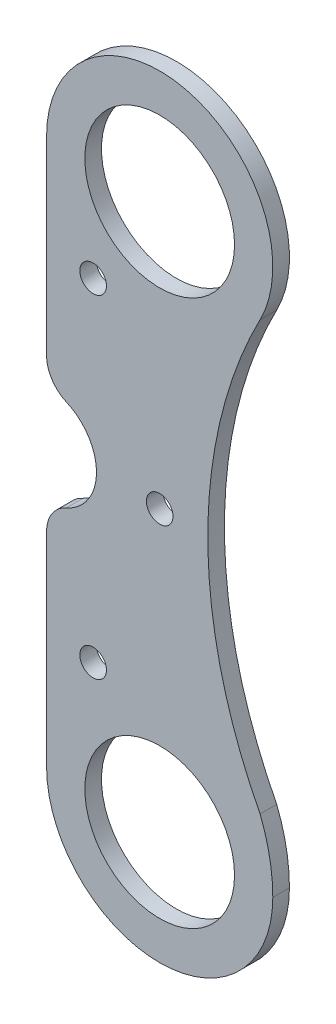
SolidWorks part; units mm, degrees
material "6061 Alloy"
ref_plane "Front Plane" through (0, 0, 0) normal (0, 0, 1) x (1, 0, 0)
ref_plane "Top Plane" through (0, 0, 0) normal (0, 1, 0) x (1, 0, 0)
ref_plane "Right Plane" through (0, 0, 0) normal (1, 0, 0) x (0, 0, -1)
sketch "Sketch1" plane through (0, 0, 0) normal (0, 0, 1) x (1, 0, 0)
  line L0 (0, 0) -> (0, -101.6) construction
  line L1 (21.59, -120.5575) -> (-21.59, -120.5575) construction
  line L2 (-8.89, 25.4) -> (8.89, 25.4)
  line L3 (-21.59, 12.7) -> (-21.59, -117.7751)
  line L5 (21.59, 12.7) -> (21.59, -117.7751)
  line L9 (-23.3829, -122.6853) -> (-33.2033, -134.3394)
  line L10 (-36.322, 25.4) -> (20.828, 25.4) construction
  line L11 (-36.322, 25.4) -> (-36.322, -203.2) construction
  line L12 (-36.322, -203.2) -> (20.828, -203.2) construction
  line L13 (20.828, 25.4) -> (20.828, -203.2) construction
  line L15 (-7.9527, -155.6168) -> (19.7971, -122.6853)
  line L16 (-32.4392, -143.2871) -> (-16.9004, -156.3809)
  circle A0 centre (0, 0) radius 38.1 construction
  circle A1 centre (0, -101.6) radius 38.1 construction
  circle A2 centre (0, 0) radius 14.2875
  circle A3 centre (0, -101.6) radius 14.2875
  arc A6 (8.89, 25.4) -> (21.59, 12.7) centre (8.89, 12.7) cw
  arc A7 (-8.89, 25.4) -> (-21.59, 12.7) centre (-8.89, 12.7) ccw
  circle A10 centre (-18.5321, -142.5501) radius 2.54
  arc A13 (-23.3829, -122.6853) -> (-21.59, -117.7751) centre (-29.21, -117.7751) ccw
  arc A14 (19.7971, -122.6853) -> (21.59, -117.7751) centre (13.97, -117.7751) ccw
  arc A15 (-16.9004, -156.3809) -> (-7.9527, -155.6168) centre (-12.8086, -151.525) ccw
  arc A16 (-33.2033, -134.3394) -> (-32.4392, -143.2871) centre (-28.3474, -138.4312) ccw
  circle A17 centre (0, -50.8) radius 2.54
  point P13 (-192.705, 39.2708)
  point P20 (21.59, 25.4)
  point P23 (-21.59, 25.4)
  point P31 (-36.322, -138.0404)
  dimension "D2" = 76.2
  dimension "D3" = 76.2
  dimension "D4" = 28.575
  dimension "D5" = 28.575
  dimension "D10" = 228.6
  dimension "D11" = 36.322
  dimension "D13" = 5.08
  dimension "D19" = 6.35
  dimension "D20" = 7.62
  dimension "D21" = 12.7
  dimension "D22" = 5.08
  dimension "D1" = 101.6
  dimension "D6" = 43.18
  dimension "D7" = 21.59
  dimension "D8" = 25.4
  dimension "D9" = 57.15
  dimension "D12" = 25.4
  dimension "D14" = 33.02
  dimension "D15" = 16.51
  dimension "D16" = 21.59
  dimension "D17" = 9.525
  dimension "D18" = 18.9575
extrude "Boss-Extrude1" add sketch "Sketch1" along normal blind 3.175
sketch "Sketch2" plane through (0, 0, 0) normal (0, 0, 1) x (1, 0, 0)
  line L0 (-21.59, -41.275) -> (-21.59, -60.325)
  line L1 (0, 0) -> (0, -101.6) construction
  line L4 (21.59, -117.7751) -> (21.59, 12.7) construction
  line L5 (-21.59, -50.8) -> (97.79, -50.8) construction
  line L6 (-21.59, 12.7) -> (-21.59, -117.7751) construction
  line L7 (0, 0) -> (-39.9512, 0) construction
  line L9 (16.51, -115.5122) -> (-17.5013, -155.8745)
  line L10 (-32.4392, -143.2871) -> (-16.9004, -156.3809) construction
  line L11 (-7.9527, -155.6168) -> (19.7971, -122.6853) construction
  line L13 (27.94, -121.6567) -> (-7.6203, -163.8572)
  line L14 (-7.6203, -163.8572) -> (-17.5013, -155.8745)
  line L15 (27.94, -121.6567) -> (27.94, 0)
  line L16 (27.94, 0) -> (21.59, 0)
  arc A1 (19.1591, -91.6472) -> (19.1591, -9.9528) centre (97.79, -50.8) cw
  arc A2 (-21.59, -60.325) -> (-21.59, -41.275) centre (-21.59, -50.8) ccw
  arc A3 (21.59, 0) -> (19.1591, -9.9528) centre (0, 0) cw
  arc A4 (21.59, -101.6) -> (19.1591, -91.6472) centre (0, -101.6) ccw
  arc A5 (21.59, -101.6) -> (16.51, -115.5122) centre (0, -101.6) cw
  dimension "D2" = 12.7
  dimension "D3" = 50.8
  dimension "D4" = 6.35
  dimension "D1" = 76.2
  dimension "D5" = 19.05
extrude "Cut-Extrude1" cut sketch "Sketch2" along normal through all contours A1 A3 L16 L15 L13 L14 L9 A5 A4 | L0 A2
sketch "Sketch3" plane through (0, 0, 3.175) normal (0, 0, 1) x (1, 0, 0)
  line L0 (-27.3514, -127.3948) -> (-36.0255, -137.6886)
  line L3 (-27.3514, -127.3948) -> (-7.5576, -144.074)
  line L4 (-23.3829, -122.6853) -> (-33.2033, -134.3394) construction
  line L5 (16.51, -115.5122) -> (-17.5013, -155.8745) construction
  line L7 (-35.4064, -144.9387) -> (-24.4031, -154.2106)
  line L8 (-23.3829, -122.6853) -> (-33.2033, -134.3394) construction
  line L9 (-7.5576, -144.074) -> (-15.4554, -153.4465)
  line L10 (-32.4392, -143.2871) -> (-17.5013, -155.8745) construction
  circle A2 centre (-18.5321, -142.5501) radius 2.54
  circle A3 centre (-18.5321, -142.5501) radius 2.54 construction
  arc A5 (-36.0255, -137.6886) -> (-35.4064, -144.9387) centre (-32.0909, -141.0041) ccw
  arc A6 (-24.4031, -154.2106) -> (-15.4554, -153.4465) centre (-20.3113, -149.3547) ccw
  dimension "D2" = 6.35
  dimension "D3" = 5.1453
  dimension "D1" = 3.175
fillet "Fillet3" radius 6.35 2 edges at (-21.59, -41.275, 1.5875) (-21.59, -60.325, 1.5875)
extrude "Boss-Extrude3" add sketch "Sketch3" against normal blind 3.175
sketch "Sketch6" plane through (0, 0, 3.175) normal (0, 0, 1) x (1, 0, 0)
  line L0 (-35.4064, -144.9387) -> (-63.6204, -121.1641)
  line L1 (-63.6204, -121.1641) -> (-51.345, -106.5965)
  line L2 (-51.345, -106.5965) -> (-27.0656, -127.0555)
  line L4 (-35.4064, -144.9387) -> (-24.4031, -154.2106) construction
  line L5 (-23.3829, -122.6853) -> (-36.0255, -137.6886) construction
  line L6 (-35.4064, -144.9387) -> (-27.0656, -127.0555)
  circle A0 centre (-52.6268, -117.9721) radius 2.54
  dimension "D4" = 5.08
  dimension "D1" = 31.75
  dimension "D2" = 9.525
  dimension "1" = 19.05
  dimension "D3" = 6.35
extrude "Boss-Extrude4" add sketch "Sketch6" against normal blind 3.175
fillet "Fillet2" radius 6.35 3 edges at (-63.6204, -121.1641, 1.5875) (-51.345, -106.5965, 1.5875) (-27.0656, -127.0555, 1.5875)
sketch "Sketch7" plane through (0, 0, 3.175) normal (0, 0, 1) x (1, 0, 0)
  line L0 (-21.59, 12.7) -> (-21.59, -36.2503) construction
  line L1 (21.59, 0) -> (21.59, 12.7) construction
  line L2 (-21.59, 0) -> (21.59, 0) construction
  line L3 (-21.59, 0) -> (-21.59, 31.75)
  line L4 (-21.59, 31.75) -> (21.59, 31.75)
  line L5 (21.59, 31.75) -> (21.59, 0)
  line L6 (8.89, 25.4) -> (-8.89, 25.4) construction
  arc A0 (-21.59, 0) -> (21.59, 0) centre (0, 0) cw
  dimension "D1" = 6.35
extrude "Cut-Extrude2" cut sketch "Sketch7" against normal through all
sketch "Sketch10" plane through (0, 0, 3.175) normal (0, 0, 1) x (1, 0, 0)
  line L0 (16.51, -115.5122) -> (-17.5013, -155.8745) construction
  line L1 (-18.1519, -155.3263) -> (-17.3615, -157.512)
  line L2 (-17.3615, -157.512) -> (-14.3757, -156.4323)
  line L3 (-14.3757, -156.4323) -> (-15.4554, -153.4465)
  line L5 (-18.1519, -155.3263) -> (-17.5013, -155.8745) construction
  circle A0 centre (-20.3113, -149.3547) radius 6.35 construction
  arc A1 (-24.4031, -154.2106) -> (-18.1519, -155.3263) centre (-20.3113, -149.3547) ccw construction
  arc A2 (-18.1519, -155.3263) -> (-15.4554, -153.4465) centre (-20.3113, -149.3547) ccw
  dimension "D1" = 3.175
  dimension "D2" = 30
extrude "Cut-Extrude3" cut sketch "Sketch10" against normal through all
sketch "Sketch12" plane through (0, 0, 3.175) normal (0, 0, 1) x (1, 0, 0)
  line L0 (-21.59, -65.3497) -> (-21.59, -117.7751) construction
  line L1 (-21.59, -101.6) -> (-72.39, -101.6)
  line L2 (-72.39, -101.6) -> (-72.39, -165.1)
  line L3 (-72.39, -165.1) -> (16.51, -165.1)
  line L4 (16.51, -165.1) -> (16.51, -115.5122)
  arc A2 (16.51, -115.5122) -> (-21.59, -101.6) centre (0, -101.6) cw
  dimension "D1" = 63.5
  dimension "D2" = 88.9
extrude "Cut-Extrude4" cut sketch "Sketch12" against normal through all
sketch "Sketch13" plane through (0, 0, 3.175) normal (0, 0, 1) x (1, 0, 0)
  line L0 (-21.59, -101.6) -> (-21.59, -104.2391)
  line L1 (21.59, -101.6) -> (21.59, -104.2391)
  line L2 (-21.59, -101.6) -> (-7.35, -118.3664)
  line L3 (-7.35, -118.3664) -> (6.6629, -118.3664)
  line L4 (6.6629, -118.3664) -> (21.59, -101.6)
  arc A0 (-21.59, -104.2391) -> (21.59, -104.2391) centre (0, -104.2391) ccw
  arc A1 (-21.59, -101.6) -> (19.1591, -91.6472) centre (0, -101.6) ccw construction
  dimension "D1" = 2.6391
extrude "Boss-Extrude7" add sketch "Sketch13" against normal through all contours A0 L1 L4 L3 L2 L0
sketch "Sketch14" plane through (0, 0, 3.175) normal (0, 0, 1) x (1, 0, 0)
  circle A0 centre (0, -101.6) radius 14.2875
  circle A1 centre (0, -101.6) radius 14.2875 construction
extrude "Boss-Extrude8" add sketch "Sketch14" against normal through all
sketch "Sketch15" plane through (0, 0, 3.175) normal (0, 0, 1) x (1, 0, 0)
  circle A0 centre (0, -104.2391) radius 14.2875
  arc A1 (-21.59, -104.2391) -> (21.59, -104.2391) centre (0, -104.2391) ccw construction
  dimension "D1" = 28.575
extrude "Cut-Extrude5" cut sketch "Sketch15" against normal through all
sketch "Sketch16" plane through (0, 0, 3.175) normal (0, 0, 1) x (1, 0, 0)
  line L0 (21.59, -104.2391) -> (21.59, -94.3525) construction
  line L1 (19.1591, -91.6472) -> (21.59, -91.6472)
  line L2 (21.59, -91.6472) -> (21.59, -104.2391)
  arc A0 (19.1591, -91.6472) -> (21.59, -104.2391) centre (-12.2375, -104.2391) cw
extrude "Cut-Extrude6" cut sketch "Sketch16" against normal through all
sketch "Sketch17" plane through (0, 0, 0) normal (0, 0, -1) x (-1, 0, 0)
  circle A0 centre (12.7, -19.05) radius 2.54
  circle A1 centre (12.7, -82.55) radius 2.54
  circle A2 centre (0, -50.8) radius 2.54 construction
  circle A3 centre (0, -50.8) radius 2.54
  dimension "D1" = 12.7
  dimension "D2" = 12.7
  dimension "D3" = 31.75
  dimension "D4" = 31.75
extrude "Cut-Extrude7" cut sketch "Sketch17" against normal through all
